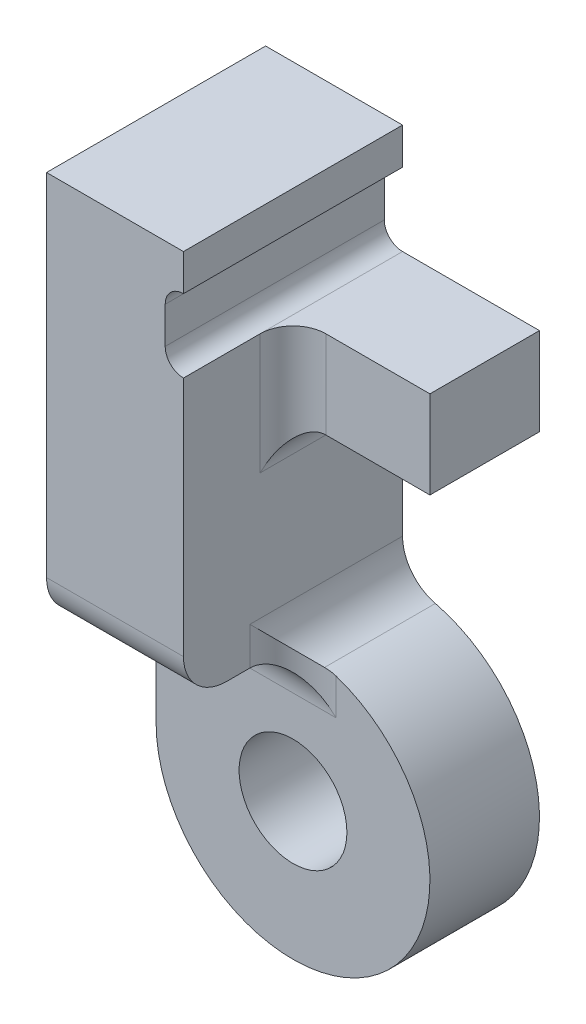
SolidWorks part; units mm, degrees
ref_plane "Front Plane" through (0, 0, 0) normal (0, 0, 1) x (1, 0, 0)
ref_plane "Top Plane" through (0, 0, 0) normal (0, 1, 0) x (1, 0, 0)
ref_plane "Right Plane" through (0, 0, 0) normal (1, 0, 0) x (0, 0, -1)
sketch "Sketch1" plane through (0, 0, 0) normal (0, 0, 1) x (1, 0, 0)
  line L0 (-3.175, 0) -> (-3.175, 12.309)
  line L1 (-3.175, 12.309) -> (0, 12.309)
  line L2 (0, 12.309) -> (0, 3.175)
  circle A0 centre (0, 0) radius 1.25
  arc A1 (-3.175, 0) -> (0, 3.175) centre (0, 0) ccw
  dimension "D1" = 2.5
  dimension "D2" = 6.35
  dimension "D3" = 12.309
extrude "Boss-Extrude1" add sketch "Sketch1" along normal blind 5.08
ref_plane "Plane1" through (0, 0, 2.54) normal (0, 0, 1) x (1, 0, 0)
sketch "Sketch3" plane through (0, 0, 2.54) normal (0, 0, 1) x (1, 0, 0)
  line L0 (0, 3.175) -> (-3.175, 3.175)
  line L1 (-3.175, 12.309) -> (-3.175, 0) construction
  line L2 (-3.175, 3.175) -> (-3.175, 0)
  arc A0 (-3.175, 0) -> (0, 3.175) centre (0, 0) ccw
extrude "Cut-Extrude1" cut sketch "Sketch3" along normal up to next
sketch "Sketch5" plane through (-3.175, 0, 0) normal (-1, 0, 0) x (0, 0, 1)
  line L0 (3.048, 4.191) -> (3.048, 11.293)
  line L1 (5.08, 3.175) -> (2.54, 3.175) construction
  line L2 (3.048, 11.293) -> (2.032, 11.293)
  line L3 (2.032, 11.293) -> (2.032, 4.191)
  line L5 (2.54, 3.175) -> (3.048, 3.175)
  line L6 (3.048, 12.309) -> (3.048, 11.293) construction
  line L7 (5.08, 12.309) -> (0, 12.309) construction
  line L8 (3.048, 11.293) -> (5.08, 11.293) construction
  line L9 (5.08, 12.309) -> (5.08, 3.175) construction
  line L10 (2.032, 11.293) -> (0, 11.293) construction
  line L11 (0, 12.309) -> (0, 0) construction
  line L12 (2.54, 3.175) -> (2.54, 3.683)
  line L13 (2.54, 3.683) -> (2.032, 4.191)
  line L14 (3.048, 4.191) -> (3.556, 3.683)
  line L15 (3.556, 3.683) -> (3.556, 3.175)
  line L16 (3.556, 3.175) -> (3.048, 3.175)
  dimension "D1" = 1.016
  dimension "D2" = 1.016
  dimension "D3" = 45
  dimension "D4" = 0.508
extrude "Cut-Extrude3" cut sketch "Sketch5" against normal blind 1.016
fillet "Fillet2" radius 1.143 1 edges at (-2.667, 3.683, 2.54)
fillet "Fillet3" radius 2.54 1 edges at (-2.667, 4.191, 2.032)
fillet "Fillet4" radius 2.54 1 edges at (-2.667, 4.191, 3.048)
fillet "Fillet5" radius 1.143 1 edges at (-2.667, 3.683, 3.556)
fillet "Fillet7" radius 1.016 1 edges at (-2.159, 11.293, 2.54)
sketch "Sketch6" plane through (0, 0, 0) normal (0, 0, -1) x (-1, 0, 0)
  line L0 (0, 7.737) -> (-3.175, 7.737)
  line L1 (0, 3.175) -> (0, 12.309) construction
  line L2 (-3.175, 7.737) -> (-3.175, 0) construction
  line L3 (-3.175, 7.737) -> (-3.175, 9.769)
  line L4 (-3.175, 9.769) -> (0, 9.769)
  line L5 (0, 12.309) -> (3.175, 12.309) construction
  line L6 (0, 9.769) -> (0, 7.737)
  arc A0 (0, 3.175) -> (3.175, 0) centre (0, 0) ccw construction
  dimension "D1" = 2.032
  dimension "D2" = 2.54
extrude "Boss-Extrude2" add sketch "Sketch6" against normal up to surface (2.54 mm away) up to face at (1.25, 0, 2.54)
fillet "Fillet8" radius 0.762 1 edges at (0, 7.737, 1.27)
sketch "Sketch8" plane through (0, 0, 0) normal (0, 0, -1) x (-1, 0, 0)
  line L0 (0, 9.769) -> (0, 12.309) construction
  line L1 (0, 9.769) -> (-3.175, 9.769) construction
  line L2 (0.4233, 11.039) -> (0.4233, 10.1923)
  line L3 (-0.4233, 11.039) -> (-0.4233, 10.1923)
  arc A0 (0.4233, 11.039) -> (-0.4233, 11.039) centre (0, 11.039) ccw
  arc A1 (-0.4233, 10.1923) -> (0.4233, 10.1923) centre (0, 10.1923) ccw
extrude "Cut-Extrude4" cut sketch "Sketch8" against normal up to next
fillet "Fillet9" radius 0.762 1 edges at (0, 8.372, 2.54)
fillet "Fillet10" radius 1 1 edges at (-1.5875, 3.175, 5.08)
fillet "Fillet11" radius 1 1 edges at (0, 3.175, 1.27)
fillet "Fillet12" radius 1 2 edges at (-1.0795, 3.175, 2.54) (0, 3.6142, 2.54)
